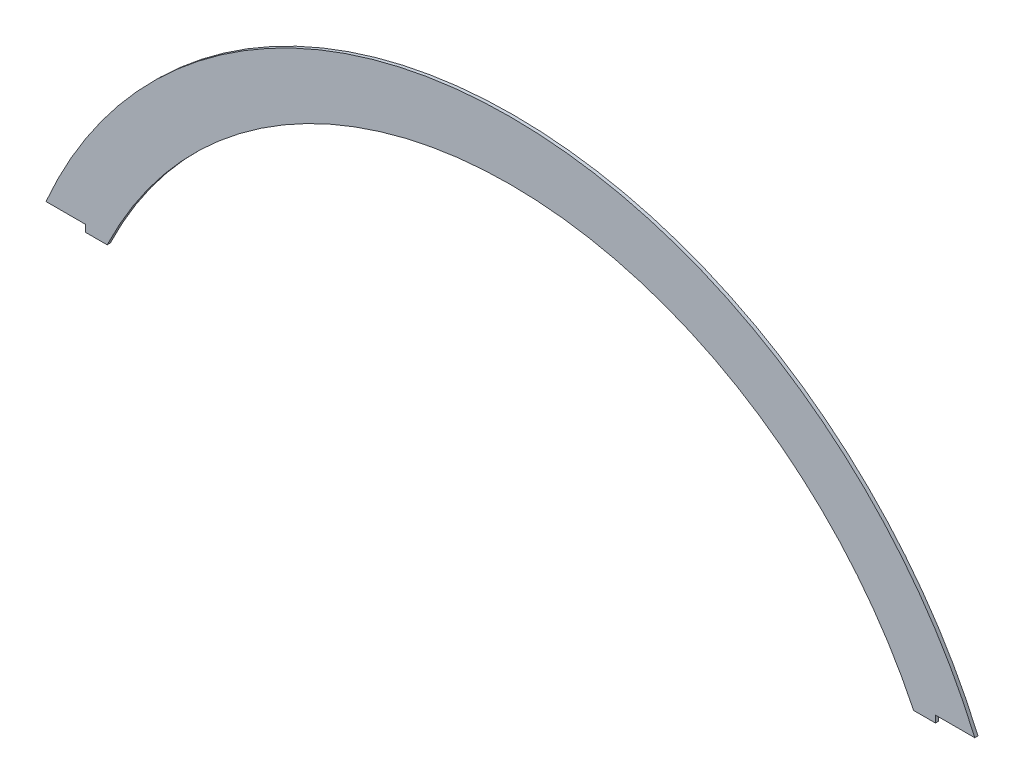
SolidWorks part; units mm, degrees
material "AISI 304"
ref_plane "Front Plane" through (0, 0, 0) normal (0, 0, 1) x (1, 0, 0)
ref_plane "Top Plane" through (0, 0, 0) normal (0, 1, 0) x (1, 0, 0)
ref_plane "Right Plane" through (0, 0, 0) normal (1, 0, 0) x (0, 0, -1)
sketch "Sketch1" plane through (0, 0, 0) normal (0, 0, 1) x (1, 0, 0)
  circle A0 centre (0, 0) radius 950
  circle A1 centre (0, 0) radius 840
  dimension "D1" = 1900
  dimension "D2" = 1680
base flange "Base-Flange1" sketch "Sketch1" thickness 6 reverse thickness direction no parameters "D1"=0
sketch "Sketch6" plane through (0, 0, 0) normal (0, 0, 1) x (1, 0, 0)
  line L1 (-1527.148, 363) -> (1205.8331, 363)
  line L2 (-1527.148, 363) -> (-1527.148, -990.8546)
  line L3 (-1527.148, -990.8546) -> (1205.8331, -990.8546)
  line L4 (1205.8331, 363) -> (1205.8331, -990.8546)
  dimension "D1" = 363
extrude "Cut-Extrude1" cut sketch "Sketch6" against normal blind 10 normal cut yes
sketch "Sketch7" plane through (0, 0, 0) normal (0, 0, 1) x (1, 0, 0)
  circle A0 centre (0, 820) radius 3.5
  dimension "D1" = 7
  dimension "D2" = 820
sketch "Sketch8" plane through (0, 0, 0) normal (0, 0, 1) x (1, 0, 0)
  line L1 (-877.9129, 363) -> (-798.5163, 363)
  line L2 (-877.9129, 363) -> (-877.9129, 376)
  line L3 (-877.9129, 376) -> (-798.5163, 376)
  line L4 (-798.5163, 363) -> (-798.5163, 376)
  dimension "D1" = 13
  dimension "D2" = 41
extrude "Cut-Extrude2" cut sketch "Sketch8" against normal blind 10
mirror "Mirror1" about plane through (0, 0, 0) normal (1, 0, 0) of "Cut-Extrude2"
sketch "Bend-Lines1" [suppressed] plane through (0, 0, 0) normal (0, 1, 0) x (1, 0, 0)
sketch "Bounding-Box1" [suppressed] plane through (0, 0, 0) normal (0, 1, 0) x (1, 0, 0)
sheet metal parameters "Sheet-Metal3" thickness 6 parameters "D1"=0
flat pattern "Flat-Pattern3" [suppressed]
sketch "Bend-Lines2" plane through (0, 0, 0) normal (0, 1, 0) x (1, 0, 0)
sketch3d "Bounding-Box2" [suppressed]
  line L0 (461.3792, -1110.0129, 0) -> (-1110.0131, -461.3787, 0) construction
  line L1 (1110.0131, 461.3788, 0) -> (-461.3792, 1110.0129, 0) construction
  line L2 (461.3792, -1110.0129, 0) -> (1110.0131, 461.3788, 0) construction
  line L3 (-1110.0131, -461.3787, 0) -> (-461.3792, 1110.0129, 0) construction
sheet metal parameters "Sheet-Metal4" thickness 6 parameters "D1"=0
flat pattern "Flat-Pattern3"
sketch "Bend-Lines2" plane through (0, 0, 0) normal (0, 1, 0) x (1, 0, 0)
sketch3d "Bounding-Box2" [suppressed]
  line L0 (-877.9129, 363, 0) -> (877.9129, 363, 0) construction
  line L1 (-877.9129, 950, 0) -> (877.9129, 950, 0) construction
  line L2 (-877.9129, 363, 0) -> (-877.9129, 950, 0) construction
  line L3 (877.9129, 363, 0) -> (877.9129, 950, 0) construction
sheet metal parameters "Sheet-Metal7" thickness 6 parameters "D1"=0
flat pattern "Flat-Pattern3"
sketch "Bend-Lines2" plane through (0, 0, 0) normal (0, 1, 0) x (1, 0, 0)
sketch3d "Bounding-Box2" [suppressed]
  line L0 (-869.3739, 363, 0) -> (877.9129, 363, 0) construction
  line L1 (-869.3739, 950, 0) -> (877.9129, 950, 0) construction
  line L2 (-869.3739, 363, 0) -> (-869.3739, 950, 0) construction
  line L3 (877.9129, 363, 0) -> (877.9129, 950, 0) construction
sheet metal parameters "Sheet-Metal8" thickness 6 parameters "D1"=0
flat pattern "Flat-Pattern3"
sketch "Bend-Lines2" plane through (0, 0, 0) normal (0, 1, 0) x (1, 0, 0)
sketch3d "Bounding-Box2" [suppressed]
  line L0 (-872.4242, 363, 0) -> (872.4242, 363, 0) construction
  line L1 (-872.4242, 950, 0) -> (872.4242, 950, 0) construction
  line L2 (-872.4242, 363, 0) -> (-872.4242, 950, 0) construction
  line L3 (872.4242, 363, 0) -> (872.4242, 950, 0) construction
